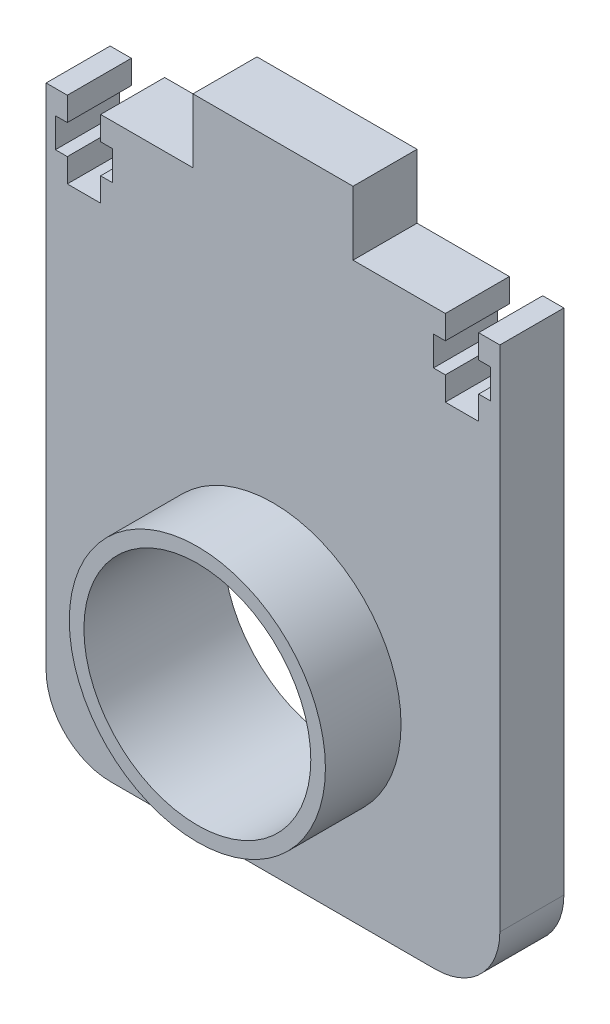
SolidWorks part; units mm, degrees
ref_plane "Front Plane" through (0, 0, 0) normal (0, 0, 1) x (1, 0, 0)
ref_plane "Top Plane" through (0, 0, 0) normal (0, 1, 0) x (1, 0, 0)
ref_plane "Right Plane" through (0, 0, 0) normal (1, 0, 0) x (0, 0, -1)
sketch "Sketch12" plane through (0, 0, 0) normal (0, 0, 1) x (1, 0, 0)
  line L0 (62.1258, 0) -> (62.1258, 126.33)
  line L1 (62.1258, 126.33) -> (152.1258, 126.33)
  line L2 (62.1258, 0) -> (152.1258, 0)
  line L3 (152.1258, 126.33) -> (152.1258, 0)
  line L4 (107.1258, 38.68) -> (107.1258, 126.33) construction
  circle A0 centre (107.1258, 38.68) radius 25.4
  circle A1 centre (107.1258, 38.68) radius 6.5
  dimension "D3" = 50.8
  dimension "D4" = 13
  dimension "D1" = 126.33
  dimension "D2" = 90
  dimension "D5" = 87.65
extrude "Boss-Extrude10" add sketch "Sketch12" along normal blind 12.7 separate body contours L1 L3 L2 L0
sketch "Sketch15" plane through (0, 0, 12.7) normal (0, 0, 1) x (1, 0, 0)
  line L0 (62.1258, 0) -> (152.1258, 0) construction
  circle A0 centre (107.1258, 38.6276) radius 25.4
  point P4 (107.1258, 0)
  dimension "D1" = 50.8
  dimension "D2" = 38.6276
extrude "Boss-Extrude11" add sketch "Sketch15" along normal blind 15
sketch "Sketch23" plane through (0, 0, 27.7) normal (0, 0, 1) x (1, 0, 0)
  circle A0 centre (107.1258, 38.6276) radius 22.5
  dimension "D1" = 45
extrude "Cut-Extrude7" cut sketch "Sketch23" against normal through all
fillet "Fillet2" radius 12.8 2 edges at (152.1258, 0, 6.35) (62.1258, 0, 6.35)
sketch "Sketch25" plane through (0, 0, 12.7) normal (0, 0, 1) x (1, 0, 0)
  line L0 (152.1258, 126.33) -> (152.1258, 113.63)
  line L1 (152.1258, 126.33) -> (152.1258, 12.8) construction
  line L2 (107.1258, 126.33) -> (107.1258, 98.7556)
  line L3 (62.1258, 12.8) -> (62.1258, 126.33) construction
  line L4 (62.1258, 113.63) -> (62.1258, 126.33)
  line L5 (123.0008, 113.63) -> (123.0008, 126.33)
  line L6 (62.1258, 126.33) -> (152.1258, 126.33) construction
  line L7 (123.0008, 126.33) -> (91.2508, 126.33)
  line L8 (91.2508, 126.33) -> (91.2508, 113.63)
  line L9 (91.2508, 113.63) -> (107.1258, 113.63)
  line L10 (107.1258, 113.63) -> (123.0008, 113.63)
  line L11 (152.1258, 113.63) -> (123.0008, 113.63)
  line L12 (123.0008, 126.33) -> (91.2508, 126.33)
  line L13 (91.2508, 113.63) -> (62.1258, 113.63)
  line M10 (152.1258, 12.8) -> (152.1258, 126.33)
  line M11 (152.1258, 126.33) -> (62.1258, 126.33)
  line M12 (62.1258, 126.33) -> (62.1258, 12.8)
  dimension "D1" = 12.7
  dimension "D2" = 31.75
extrude "Cut-Extrude9" cut sketch "Sketch25" against normal through all contours L13 L8 M11 M12 | L11 L5 M10 M11 region at (137.5633, 119.98, 12.7) region at (76.6883, 119.98, 12.7)
sketch "Sketch27" plane through (0, 0, 12.7) normal (0, 0, 1) x (1, 0, 0)
  line L0 (147.9178, 113.63) -> (147.9178, 108.931)
  line L1 (152.1258, 113.63) -> (123.0008, 113.63) construction
  line L2 (147.9178, 108.931) -> (150.2798, 108.931)
  line L3 (150.2798, 108.931) -> (150.2798, 103.089)
  line L4 (150.2798, 103.089) -> (147.9178, 103.089)
  line L5 (147.9178, 103.089) -> (147.9178, 98.39)
  line L6 (147.9178, 98.39) -> (141.3138, 98.39)
  line L7 (141.3138, 98.39) -> (141.3138, 103.089)
  line L8 (141.3138, 103.089) -> (138.9518, 103.089)
  line L9 (138.9518, 103.089) -> (138.9518, 108.931)
  line L10 (138.9518, 108.931) -> (141.3138, 108.931)
  line L11 (141.3138, 108.931) -> (141.3138, 113.63)
  line L12 (107.1258, 126.33) -> (107.1258, 67.6415) construction
  line L13 (91.2508, 126.33) -> (123.0008, 126.33) construction
  line L14 (72.9378, 103.089) -> (75.2998, 103.089)
  line L15 (75.2998, 103.089) -> (75.2998, 108.931)
  line L16 (75.2998, 108.931) -> (72.9378, 108.931)
  line L17 (72.9378, 108.931) -> (72.9378, 113.63)
  line L18 (66.3338, 113.63) -> (66.3338, 108.931)
  line L19 (66.3338, 108.931) -> (63.9718, 108.931)
  line L20 (63.9718, 108.931) -> (63.9718, 103.089)
  line L21 (63.9718, 103.089) -> (66.3338, 103.089)
  line L22 (66.3338, 103.089) -> (66.3338, 98.39)
  line L23 (66.3338, 98.39) -> (72.9378, 98.39)
  line L24 (72.9378, 98.39) -> (72.9378, 103.089)
  line L25 (147.9178, 113.63) -> (141.3138, 113.63)
  line L26 (72.9378, 113.63) -> (66.3338, 113.63)
  point P30 (144.6158, 113.63)
  point P31 (69.6358, 113.63)
  dimension "D1" = 6.604
  dimension "D2" = 11.328
  dimension "D3" = 15.24
  dimension "D4" = 5.842
  dimension "D5" = 74.98
ref_axis "Axis1" through (107.1258, 126.33, 12.7) along (0, -1, 0)
extrude "Cut-Extrude10" cut sketch "Sketch27" against normal through all
